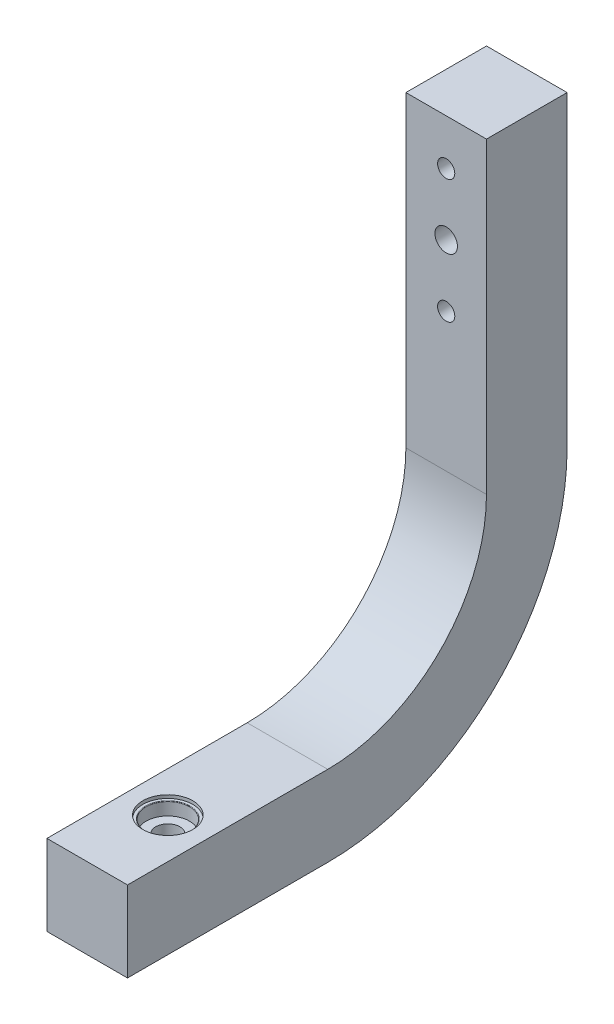
SolidWorks part; units mm, degrees
ref_plane "Front Plane" through (0, 0, 0) normal (0, 0, 1) x (1, 0, 0)
ref_plane "Top Plane" through (0, 0, 0) normal (0, 1, 0) x (1, 0, 0)
ref_plane "Right Plane" through (0, 0, 0) normal (1, 0, 0) x (0, 0, -1)
ref_axis "Z" through (0, 0, 85.8948) along (0, 0, -1)
sketch "Sketch1" plane through (0, 0, 0) normal (1, 0, 0) x (0, 0, -1)
  line L0 (-15, 20) -> (0, 20)
  line L1 (0, 20) -> (0, -37.2682)
  line L2 (0, -32) -> (-49.8046, -81.8046) construction
  line L3 (-44.5364, -81.8046) -> (-66.8046, -81.8046)
  line L4 (-66.8046, -81.8046) -> (-66.8046, -66.8046) construction
  line L5 (-66.8046, -66.8046) -> (-44.5364, -66.8046)
  line L6 (-56.0178, -66.8046) -> (-15, -25.7868) construction
  line L7 (-15, -37.2682) -> (-15, 20)
  line L8 (-35.5089, -46.2957) -> (-24.9023, -56.9023) construction
  line L9 (-44.5364, -66.8046) -> (-56.0178, -66.8046) construction
  line L10 (-66.8046, -66.8046) -> (-81.8046, -66.8046)
  line L11 (-66.8046, -66.8046) -> (-66.8046, -81.8046) construction
  line L12 (-66.8046, -81.8046) -> (-81.8046, -81.8046)
  line L13 (-81.8046, -66.8046) -> (-81.8046, -81.8046)
  line L14 (-15, -25.7868) -> (-15, -37.2682) construction
  line L15 (0, -37.2682) -> (0, -32) construction
  line L16 (-49.8046, -81.8046) -> (-44.5364, -81.8046) construction
  arc A0 (-44.5364, -66.8046) -> (-15, -37.2682) centre (-44.5364, -37.2682) ccw
  arc A1 (-44.5364, -81.8046) -> (0, -37.2682) centre (-44.5364, -37.2682) ccw
  dimension "D1" = 15
  dimension "D2" = 66.8046
  dimension "D3" = 81.8046
  dimension "D4" = 20
  dimension "D5" = 135
  dimension "D6" = 49.8046
  dimension "D7" = 15
  dimension "D8" = 22.2682
extrude "Boss-Extrude1" add sketch "Sketch1" along normal blind 7.5 and the other way blind 7.5
sketch "Sketch3" plane through (0, -66.8046, 0) normal (0, 1, 0) x (1, 0, 0)
  line L0 (-8.25, 0) -> (8.25, 0) construction
  line L1 (0, -44.9925) -> (0, 44.9925) construction
  circle A0 centre (0, -66.8046) radius 2.25
  dimension "D2" = 4.5
  dimension "D1" = 66.8046
extrude "Cut-Extrude1" cut sketch "Sketch3" against normal through all
sketch "Sketch4" plane through (0, 0, 15) normal (0, 0, 1) x (1, 0, 0)
  line L0 (0, -11.5) -> (0, 11.5) construction
  circle A0 centre (0, 0) radius 2.1
  circle A1 centre (0, 11.5) radius 1.6
  circle A2 centre (0, -11.5) radius 1.6
  dimension "D1" = 4.2
  dimension "D3" = 3.2
  dimension "D2" = 23
extrude "Cut-Extrude2" cut sketch "Sketch4" against normal through all both and the other way through all
ref_axis "Axis1" through (0, -52.1687, 66.8046) along (0, 1, 0)
sketch "Sketch5" plane through (0, 0, 0) normal (1, 0, 0) x (0, 0, -1)
  line L0 (-62.7546, -78.8046) -> (-62.7546, -81.1046)
  line L1 (-62.6546, -81.2046) -> (-62.1546, -81.2046)
  line L2 (-62.1546, -81.2046) -> (-62.1546, -81.8046)
  line L3 (-62.1546, -81.8046) -> (-66.8046, -81.8046)
  line L4 (-66.8046, -81.8046) -> (-66.8046, -78.8046)
  line L5 (-66.8046, -78.8046) -> (-62.7546, -78.8046)
  line L6 (-66.8046, -74.3046) -> (-66.8046, -90.6731) construction
  line L7 (-66.8046, -74.3046) -> (-81.8046, -74.3046) construction
  line L8 (-66.8046, -69.8046) -> (-62.7546, -69.8046)
  line L9 (-66.8046, -66.8046) -> (-66.8046, -69.8046)
  line L10 (-62.1546, -66.8046) -> (-66.8046, -66.8046)
  line L11 (-62.1546, -67.4046) -> (-62.1546, -66.8046)
  line L12 (-62.6546, -67.4046) -> (-62.1546, -67.4046)
  line L13 (-62.7546, -69.8046) -> (-62.7546, -67.5046)
  line L16 (-66.8046, -52.1687) -> (-66.8046, -36.5447) construction
  line L17 (-81.8046, -66.8046) -> (-81.8046, -81.8046) construction
  line L18 (-66.8046, -66.8046) -> (-44.5364, -66.8046) construction
  arc A0 (-62.7546, -67.5046) -> (-62.6546, -67.4046) centre (-62.6546, -67.5046) cw
  arc A1 (-62.6546, -81.2046) -> (-62.7546, -81.1046) centre (-62.6546, -81.1046) cw
  point P23 (-62.7546, -67.4046)
  point P26 (-62.7546, -81.2046)
  dimension "D5" = 0.1
  dimension "D6" = 0.1
  dimension "D2" = 4.65
  dimension "D3" = 3
  dimension "D4" = 8.1
revolve "Cut-Revolve1" cut sketch "Sketch5" angle 360 about axis through (0, -52.1687, 66.8046) along (0, 1, 0)
equation "\"rbracket-width\"= \"L2Thickness\""
equation "\"D1@Boss-Extrude1\"=\"rbracket-width\"/2"
equation "\"D2@Boss-Extrude1\"=\"rbracket-width\"/2"
equation "\"EyeCaptureRadius\"= ( \"EyeDiameter\" + \"EyeClearance\" ) / 2"
equation "\"rbracket_planetocenterline_dist\"= \"BasePlaneDistance\""
equation "\"D2@Sketch1\"=\"rbracket_planetocenterline_dist\""
equation "\"EyeDiameter\" = 99.60916292"
equation "\"BasePlaneDistance\" = \"EyeDiameter\"/2+\"L2Thickness\"+\"EyeClearance\""
equation "\"EyeClearance\" = 2"
equation "\"D1@Sketch1\"=\"rbracket-width\""
equation "\"D3@Sketch1\"=(\"EyeDiameter\"+\"EyeClearance\"+\"EyeClearance\")/2 + \"L2Thickness\" + \"rbracket-width\""
equation "\"D6@Sketch1\"=\"EyeDiameter\"/2"
equation "\"D7@Sketch1\"=\"rbracket-width\""
equation "\"D1@Sketch3\"=\"BasePlaneDistance\""
equation "\"L2Thickness\" = 3.75 * \"shaft_diameter\""
equation "\"D8@Sketch1\"=\"rbracket_planetocenterline_dist\"/3"
equation "\"BearingFlangeOD\"= 7.5"
equation "\"BearingFlangeThickness\"= 0.75"
equation "\"BearingHousingID\"=4.5"
equation "\"BearingDepth\"= 6"
equation "\"PrinterFilamentThickness\"= 0.1"
equation "\"ApplyPrinterOffsets\"= 1"
equation "\"L2_ID\" = 20"
equation "\"vx\" = 0"
equation "\"vy\" = 0"
equation "\"vz\" = 200"
equation "\"parametric_end\" = 1"
equation "\"Rw_3_xx\" = -(\"vz\")/sqr((\"vx\")^2 + (\"vz\")^2)"
equation "\"Rw_3_xy\" = 0"
equation "\"Rw_3_xz\" = (\"vx\")/sqr((\"vx\")^2 + (\"vz\")^2)"
equation "\"Rw_3_zx\" = (\"vx\")/sqr((\"vx\")^2 + (\"vy\")^2 + (\"vz\")^2)"
equation "\"Rw_3_zy\" = (\"vy\")/sqr((\"vx\")^2 + (\"vy\")^2 + (\"vz\")^2)"
equation "\"Rw_3_zz\" = (\"vz\")/sqr((\"vx\")^2 + (\"vy\")^2 + (\"vz\")^2)"
equation "\"Rw_3_yx\" = (\"vx\")*(\"vy\")/sqr((\"vx\")^4 + (\"vx\")^2*(\"vy\")^2 + 2*(\"vx\")^2*(\"vz\")^2 + (\"vy\")^2*(\"vz\")^2 + (\"vz\")^4)"
equation "\"Rw_3_yy\" = -sqr((\"vx\")^2 + (\"vz\")^2)/sqr((\"vx\")^2 + (\"vy\")^2 + (\"vz\")^2)"
equation "\"Rw_3_yz\" = (\"vy\")*(\"vz\")/sqr((\"vx\")^4 + (\"vx\")^2*(\"vy\")^2 + 2*(\"vx\")^2*(\"vz\")^2 + (\"vy\")^2*(\"vz\")^2 + (\"vz\")^4)"
equation "\"O2Targx\" = -\"BasePlaneDistance\"*(\"vx\")*(\"vy\")/sqr((\"vx\")^4 + (\"vx\")^2*(\"vy\")^2 + 2*(\"vx\")^2*(\"vz\")^2 + (\"vy\")^2*(\"vz\")^2 + (\"vz\")^4)"
equation "\"O2Targy\" = \"BasePlaneDistance\"*sqr((\"vx\")^2 + (\"vz\")^2)/sqr((\"vx\")^2 + (\"vy\")^2 + (\"vz\")^2)"
equation "\"O2Targz\" = -\"BasePlaneDistance\"*(\"vy\")*(\"vz\")/sqr((\"vx\")^4 + (\"vx\")^2*(\"vy\")^2 + 2*(\"vx\")^2*(\"vz\")^2 + (\"vy\")^2*(\"vz\")^2 + (\"vz\")^4)"
equation "\"O2Targx_0\" = -(\"BasePlaneDistance\")*sqr((\"vx\")^2 + (\"vz\")^2)/sqr((\"vx\")^2 + (\"vy\")^2 + (\"vz\")^2)"
equation "\"O2Targy_0\" = -(\"BasePlaneDistance\")*(\"vy\")*(\"vz\")/sqr((\"vx\")^4 + (\"vx\")^2*(\"vy\")^2 + 2*(\"vx\")^2*(\"vz\")^2 + (\"vy\")^2*(\"vz\")^2 + (\"vz\")^4)"
equation "\"O2Targz_0\" = (\"BasePlaneDistance\")*(\"vx\")*(\"vy\")/sqr((\"vx\")^4 + (\"vx\")^2*(\"vy\")^2 + 2*(\"vx\")^2*(\"vz\")^2 + (\"vy\")^2*(\"vz\")^2 + (\"vz\")^4) + (\"BasePlaneDistance\")"
equation "\"theta2_s1\" = arcsin(((\"BasePlaneDistance\") - (\"O2Targz_0\"))/(\"BasePlaneDistance\")) + pi"
equation "\"theta2_s2\" = -arcsin(((\"BasePlaneDistance\") - (\"O2Targz_0\"))/(\"BasePlaneDistance\"))"
equation "\"theta1_s1\" = arcsin((\"O2Targy_0\")/((\"BasePlaneDistance\")*cos((\"Theta2\")))) + pi"
equation "\"theta1_s2\" = -arcsin((\"O2Targy_0\")/((\"BasePlaneDistance\")*cos((\"Theta2\"))))"
equation "\"theta1_s3\" = -arccos(-(\"O2Targx_0\")/((\"BasePlaneDistance\")*cos((\"Theta2\")))) + 2*pi"
equation "\"theta1_s4\" = arccos(-(\"O2Targx_0\")/((\"BasePlaneDistance\")*cos((\"Theta2\"))))"
equation "\"Theta1\" = \"theta1_s2\" 'so far, theta1_s1 and theta1_s4 have agreed, and they agree with the sw constraint solver"
equation "\"Theta2\" = \"theta2_s2\""
equation "\"o2_x\" = -(\"BasePlaneDistance\")*cos((\"Theta1\"))*cos((\"Theta2\"))"
equation "\"o2_y\" = -(\"BasePlaneDistance\")*sin((\"Theta1\"))*cos((\"Theta2\"))"
equation "\"o2_z\" = (\"BasePlaneDistance\")*(sin((\"Theta2\")) + 1)"
equation "\"o1_x\" = (\"BasePlaneDistance\")*sin((\"Theta1\"))"
equation "\"o1_y\" = -(\"BasePlaneDistance\")*cos((\"Theta1\"))"
equation "\"o1_z\" = (\"BasePlaneDistance\")"
equation "\"Actuator1_Theta\" = atn(\"vx\"/\"vz\") 'ik solution for the single link joint"
equation "\"Actuator2_Theta\" = \"Theta1\"  'ik solution for the double link joint"
equation "\"MotorBaseThickness\" = 3 "
equation "\"BaseThickness\" = 3 "
equation "\"EncoderToMagnetAirgap\" = 1 'Encoder to magnet airgap"
equation "\"EncoderHeight\" = 1.192  'Height of the encoder"
equation "\"MagnetThickness\" = 0.5  'Magnet thickness"
equation "\"pcb_thickness\" = 1.6  'Thickness of the PCB"
equation "\"pcb_outer_diameter\" = 32 'the OD of the pcb"
equation "\"shaft_diameter\" = 4"
equation "\"D2@Sketch3\"=\"shaft_diameter\"*1.125"
equation "\"D2@Sketch5\"=\"ApplyPrinterOffsets\"*\"PrinterFilamentThickness\"/2+4.6"
equation "\"D4@Sketch5\"=\"ApplyPrinterOffsets\"*\"PrinterFilamentThickness\"+8"
